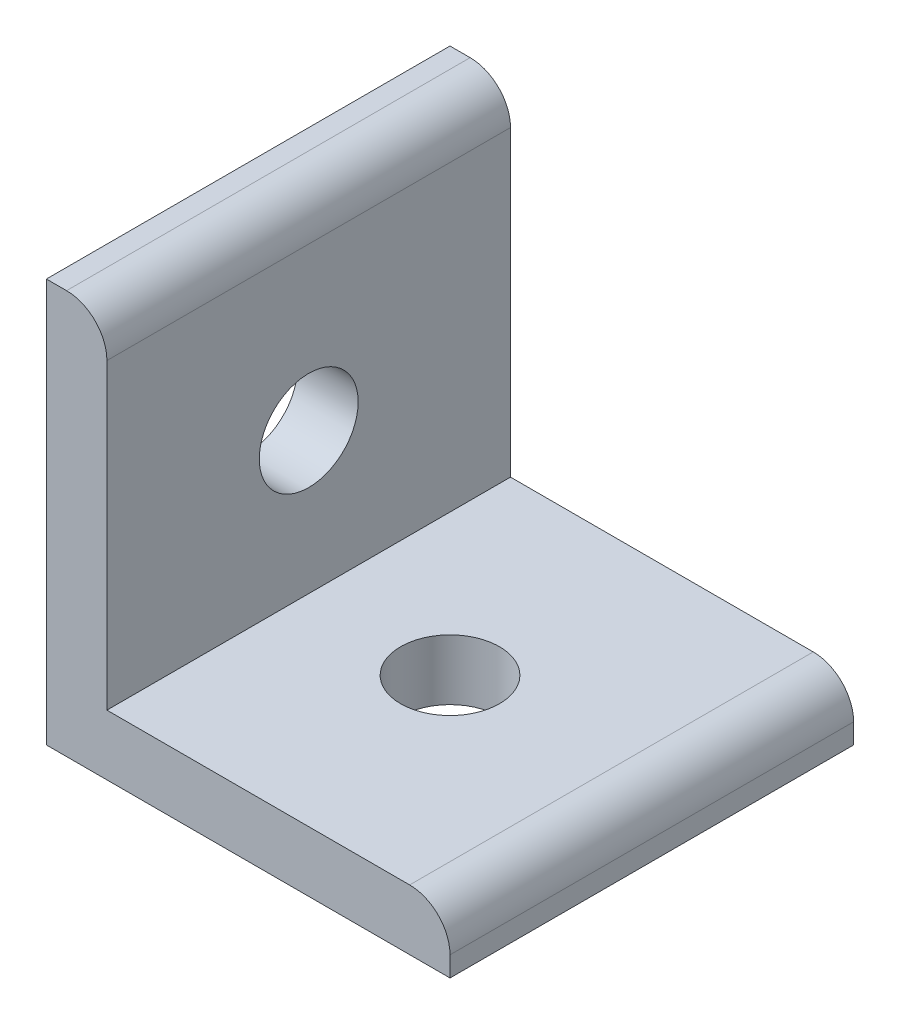
SolidWorks part; units mm, degrees
ref_plane "前视基准面" through (0, 0, 0) normal (0, 0, 1) x (1, 0, 0)
ref_plane "上视基准面" through (0, 0, 0) normal (0, 1, 0) x (1, 0, 0)
ref_plane "右视基准面" through (0, 0, 0) normal (1, 0, 0) x (0, 0, -1)
sketch "草图1" plane through (0, 0, 0) normal (0, 0, 1) x (1, 0, 0)
  line L0 (0, 0) -> (20.0016, 0)
  line L1 (0, 0) -> (0, 19.9969)
  line L2 (0, 19.9969) -> (2.9992, 19.9969)
  line L3 (2.9992, 19.9969) -> (2.9992, 2.9944)
  line L4 (2.9992, 2.9944) -> (20.0016, 2.9944)
  line L5 (20.0016, 2.9944) -> (20.0016, 0)
  dimension "D1" = 17.0024
  dimension "D2" = 17.0024
  dimension "D3" = 2.9992
  dimension "D4" = 2.9944
extrude "凸台-拉伸1" add sketch "草图1" along normal blind 20
sketch "草图3" plane through (2.9992, 0, 0) normal (1, 0, 0) x (0, 0, -1)
  line L0 (-20, 19.9969) -> (0, 19.9969) construction
  circle A0 centre (-10, 9.9969) radius 2.45
  dimension "D1" = 4.9
  dimension "D2" = 10
extrude "切除-拉伸1" cut sketch "草图3" against normal up to surface (2.9992 mm away) up to face at (0, 9.9984, 10)
sketch "草图5" plane through (0, 2.9944, 0) normal (0, 1, 0) x (1, 0, 0)
  line L0 (20.0016, -20) -> (20.0016, 0) construction
  circle A0 centre (10.0016, -10) radius 2.45
  dimension "D1" = 4.9
  dimension "D2" = 10
extrude "切除-拉伸2" cut sketch "草图5" against normal up to surface (2.9944 mm away) up to face at (10.0008, 0, 10)
fillet "圆角1" radius 2 1 edges at (2.9992, 19.9969, 10)
fillet "圆角2" radius 2 1 edges at (20.0016, 2.9944, 10)
ref_plane "Plane1" through (0, 0, 10) normal (0, 0, -1) x (-1, 0, 0)
